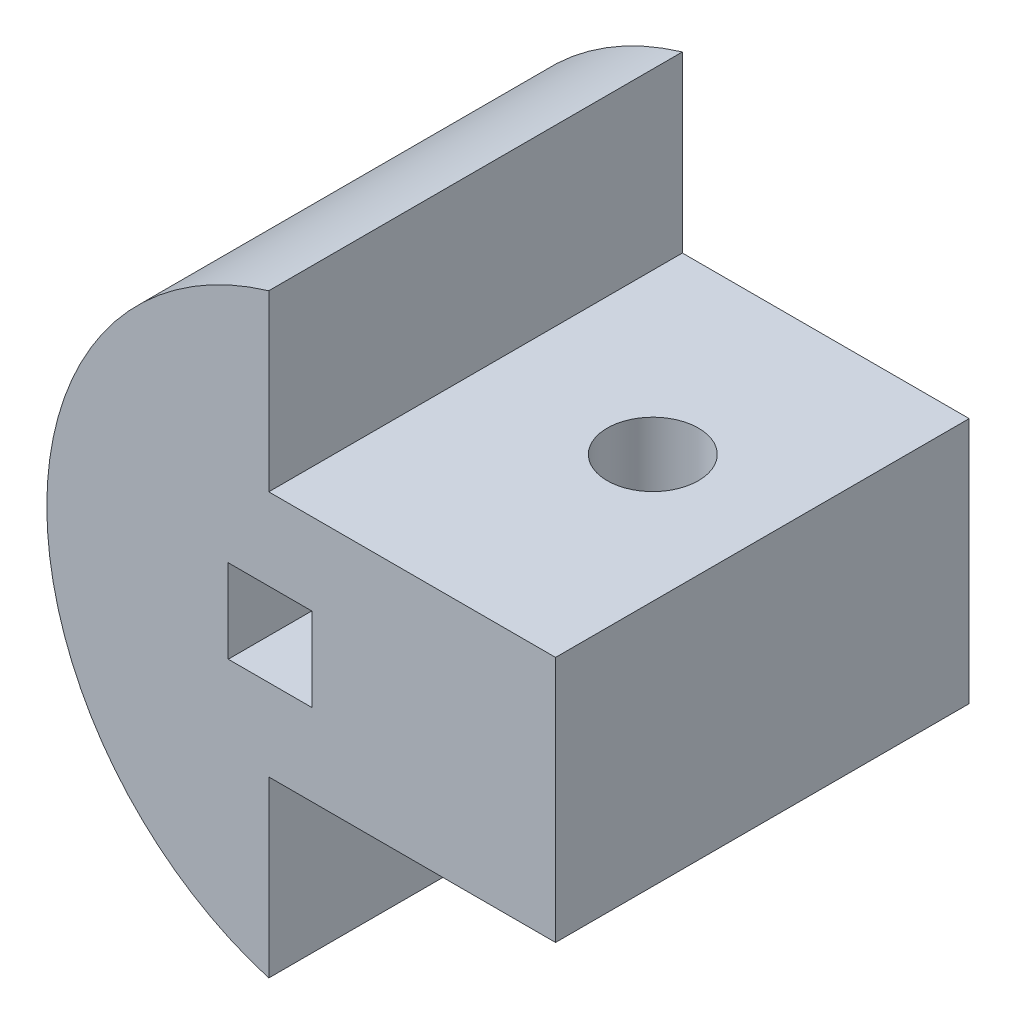
SolidWorks part; units mm, degrees
material "ABS"
ref_plane "Front Plane" through (0, 0, 0) normal (0, 0, 1) x (1, 0, 0)
ref_plane "Top Plane" through (0, 0, 0) normal (0, 1, 0) x (1, 0, 0)
ref_plane "Right Plane" through (0, 0, 0) normal (1, 0, 0) x (0, 0, -1)
sketch "Sketch2" plane through (0, 0, 0) normal (0, 0, 1) x (1, 0, 0)
  line L0 (0, 20) -> (0, 13) construction
  line L1 (0, 13) -> (11.5, 13) construction
  line L2 (11.5, 13) -> (11.5, 8) construction
  line L3 (0, 3) -> (11.5, 3) construction
  line L4 (0, -4) -> (0, 3) construction
  line L5 (11.5, 3) -> (11.5, 8) construction
  line L6 (0, 20) -> (0, 13) construction
  line L7 (0, 13) -> (11.5, 13) construction
  line L8 (11.5, 13) -> (11.5, 8) construction
  line L9 (0, 3) -> (11.5, 3) construction
  line L10 (0, -4) -> (0, 3) construction
  line L11 (11.5, 3) -> (11.5, 8) construction
  line L12 (-0.05, 19.9331) -> (-0.05, 12.95)
  line L13 (-1.675, 9.675) -> (1.675, 9.675)
  line L14 (-1.675, 9.675) -> (-1.675, 6.325)
  line L15 (-1.675, 6.325) -> (1.675, 6.325)
  line L16 (1.675, 9.675) -> (1.675, 6.325)
  line L17 (-1.675, 9.675) -> (1.675, 6.325) construction
  line L18 (-1.675, 6.325) -> (1.675, 9.675) construction
  line L19 (-0.05, 12.95) -> (11.45, 12.95)
  line L20 (11.45, 12.95) -> (11.45, 8)
  line L21 (11.45, 3.05) -> (11.45, 8)
  line L22 (-0.05, 3.05) -> (11.45, 3.05)
  line L23 (-0.05, -3.9331) -> (-0.05, 3.05)
  line L24 (0, 3) -> (0, 13) construction
  line L25 (0, 13) -> (0.029, 13.0264) construction
  arc A0 (0, 20) -> (0, -4) centre (3.5, 8) ccw construction
  arc A1 (-0.05, 19.9331) -> (-0.05, -3.9331) centre (3.5, 8) ccw
  arc A2 (0, 20) -> (0, -4) centre (3.5, 8) ccw construction
  point P7 (0, 8)
  dimension "D1" = 3.35
  dimension "D3" = 8
  dimension "D2" = 0.05
extrude "Boss-Extrude1" add sketch "Sketch2" against normal up to surface (16.586 mm away) contours L12 A1 L23 L22 L21 L20 L19 L13 L16 L15 L14 region at (-0.364, 16.4416, 0)
sketch "Sketch3" plane through (0, 0, 0) normal (0, 0, 1) x (1, 0, 0)
  line L0 (-1.675, 8) -> (1.675, 8)
  line L1 (-1.675, 9.675) -> (-1.675, 6.325) construction
  line L2 (1.675, 9.675) -> (1.675, 6.325) construction
  point P0 (0, 8)
ref_axis "Axis1" through (0, 8, 0) along (0, 0, 1)
sketch "Sketch4" plane through (0, 3.05, 0) normal (0, -1, 0) x (1, 0, 0)
  circle A0 centre (6.35, -9) radius 1.8288 construction
  circle A1 centre (6.35, -9) radius 1.8288
extrude "Cut-Extrude1" cut sketch "Sketch4" against normal through all
